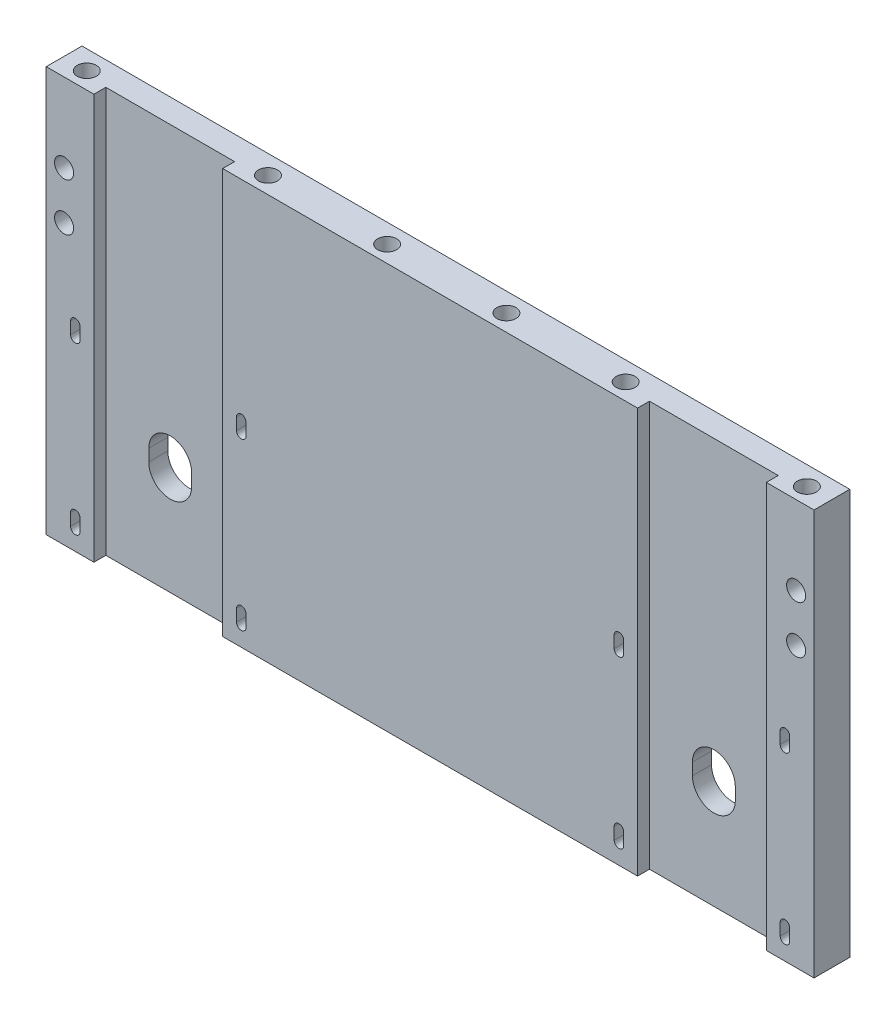
SolidWorks part; units mm, degrees
ref_plane "Płaszczyzna przednia" through (0, 0, 0) normal (0, 0, 1) x (1, 0, 0)
ref_plane "Płaszczyzna górna" through (0, 0, 0) normal (0, 1, 0) x (1, 0, 0)
ref_plane "Płaszczyzna prawa" through (0, 0, 0) normal (1, 0, 0) x (0, 0, -1)
sketch "Szkic1" plane through (0, 0, 0) normal (0, 0, 1) x (1, 0, 0)
  line L1 (161, -85) -> (-161, -85)
  line L2 (161, -85) -> (161, 85)
  line L3 (161, 85) -> (-161, 85)
  line L4 (-161, -85) -> (-161, 85)
  line L5 (161, -85) -> (-161, 85) construction
  line L6 (161, 85) -> (-161, -85) construction
  point P0 (0, 0)
  dimension "D1" = 322
  dimension "D2" = 170
extrude "Dodanie-wyciągnięcie1" add sketch "Szkic1" along normal blind 15
sketch "Szkic3" plane through (0, 0, 15) normal (0, 0, 1) x (1, 0, 0)
  line L0 (161, 85) -> (-161, 85) construction
  line L1 (-141, 85) -> (-87, 85)
  line L2 (-141, 85) -> (-141, -85)
  line L3 (-141, -85) -> (-87, -85)
  line L4 (-87, 85) -> (-87, -85)
  line L5 (-161, -85) -> (161, -85) construction
  line L6 (-161, 85) -> (-161, -85) construction
  line L7 (161, -85) -> (161, 85) construction
  line L8 (87, 85) -> (141, 85)
  line L9 (87, 85) -> (87, -85)
  line L10 (87, -85) -> (141, -85)
  line L11 (141, 85) -> (141, -85)
  dimension "D1" = 54
  dimension "D2" = 20
  dimension "D3" = 54
  dimension "D4" = 20
extrude "Wytnij-wyciągnięcie1" cut sketch "Szkic3" against normal blind 5
sketch "Szkic2" plane through (0, 0, 15) normal (0, 0, 1) x (1, 0, 0)
  line L0 (-161, -85) -> (-141, -85) construction
  line L1 (-161, 85) -> (-161, -85) construction
  line L3 (-150.8, -71.87) -> (-146.8, -71.87)
  line L4 (-150.8, -71.87) -> (-150.8, -76.87)
  line L5 (-150.8, -76.87) -> (-146.8, -76.87)
  line L6 (-146.8, -71.87) -> (-146.8, -76.87)
  circle A0 centre (-148.8, -76.87) radius 2
  circle A1 centre (-148.8, -71.87) radius 2
  dimension "D1" = 8.13
  dimension "D2" = 12.2
  dimension "D3" = 5
  dimension "D4" = 4
  dimension "D5" = 4
extrude "Wytnij-wyciągnięcie2" cut sketch "Szkic2" against normal blind 17.75 contours L3 A1 | L3 A1 | A1 L4 A0 L6 | L5 A0 | L5 A0 region at (-148.8, -71.0212, 15) region at (-148.8, -74.37, 15) region at (-148.8, -72.7188, 15) region at (-148.8, -76.0212, 15) region at (-148.8, -77.7188, 15)
pattern_linear "Szyk liniowy1" count 2 spacing 69.6 along (1, 0, 0) count 2 spacing 69.6 along (0, 1, 0) of "Wytnij-wyciągnięcie2"
sketch "Szkic5" plane through (0, 0, 0) normal (0, 0, -1) x (-1, 0, 0)
  line L0 (161, -85) -> (-161, -85) construction
  line L4 (161, 85) -> (161, -85) construction
  line L10 (150.5, -42.07) -> (77.5, -42.07)
  line L11 (150.5, -42.07) -> (150.5, -37.07)
  line L12 (150.5, -37.07) -> (77.5, -37.07)
  line L13 (77.5, -42.07) -> (77.5, -37.07)
  circle A0 centre (114, -42.07) radius 36.5
  circle A1 centre (114, -37.07) radius 36.5
  dimension "D1" = 42.93
  dimension "D3" = 73
  dimension "D4" = 5
  dimension "D5" = 73
  dimension "D2" = 47
extrude "Wytnij-wyciągnięcie3" cut sketch "Szkic5" against normal blind 2 contours L12 A1 A0 | L12 A0 | A0 A1 L10 L12 | L10 A1 | A1 L10 A0 | L12 A1 A0 | A1 A0 L10 | A1 L13 A0 | A0 A1 L12 | A1 L10 A0 | A1 A0 L11 | A1 region at (-114, -77.7538, 0) region at (-150.4743, -39.57, 0) region at (-150.3711, -41.2371, 0) region at (-114, -55.296, 0) region at (-114, -39.57, 0) region at (-150.3711, -37.9029, 0) region at (-150.328, -36.2538, 0) region at (-77.6289, -41.2371, 0) region at (-77.5257, -39.57, 0) region at (-114, -23.844, 0) region at (-77.6289, -37.9029, 0)
sketch "Szkic7" plane through (0, 0, 2) normal (0, 0, -1) x (-1, 0, 0)
  line L1 (105, -37.07) -> (123, -37.07)
  line L2 (105, -37.07) -> (105, -42.07)
  line L3 (105, -42.07) -> (123, -42.07)
  line L4 (123, -37.07) -> (123, -42.07)
  circle A0 centre (114, -42.07) radius 9
  arc A2 (77.5, -42.07) -> (150.5, -42.07) centre (114, -42.07) ccw construction
  circle A3 centre (114, -37.07) radius 9
  point P8 (114, -78.57)
  dimension "D1" = 18
  dimension "D2" = 18
extrude "Wytnij-wyciągnięcie4" cut sketch "Szkic7" against normal blind 17.75 contours A3 L3 A0 | L3 A3 | A0 A3 L3 L1 | A3 A0 L3 | L1 A3 A0 | L1 A3 A0 | A3 L2 A0 | L1 A0 | A0 A3 L1 | A3 A0 L4 | A3 L3 A0 region at (-114, -32.1697, 2) region at (-105.1059, -39.57, 2) region at (-105.5557, -37.8954, 2) region at (-114, -35.435, 2) region at (-114, -39.57, 2) region at (-105.5557, -41.2446, 2) region at (-114, -46.9703, 2) region at (-122.4443, -37.8954, 2) region at (-122.8941, -39.57, 2) region at (-114, -43.705, 2) region at (-122.4443, -41.2446, 2)
pattern_linear "Szyk liniowy2" count 2 spacing 228 along (1, 0, 0) of "Wytnij-wyciągnięcie2", "Szyk liniowy1", "Wytnij-wyciągnięcie3", "Wytnij-wyciągnięcie4"
sketch "Szkic8" plane through (0, 85, 0) normal (0, 1, 0) x (1, 0, 0)
  line L0 (-161, -15) -> (-161, 0) construction
  line L1 (-141, -15) -> (-161, -15) construction
  line L2 (161, -15) -> (161, 0) construction
  line L3 (161, -15) -> (141, -15) construction
  circle A0 centre (-151, -8) radius 4
  circle A1 centre (151, -8) radius 4
  dimension "D1" = 10
  dimension "D3" = 8
  dimension "D6" = 8
  dimension "D2" = 7
  dimension "D4" = 10
  dimension "D5" = 7
extrude "Wytnij-wyciągnięcie5" cut sketch "Szkic8" against normal blind 20
sketch "Szkic9" plane through (0, 85, 0) normal (0, 1, 0) x (1, 0, 0)
  line L0 (87, -15) -> (-87, -15) construction
  line L1 (-87, -10) -> (-87, -15) construction
  circle A0 centre (-75, -8) radius 4
  dimension "D1" = 8
  dimension "D2" = 7
  dimension "D3" = 12
extrude "Wytnij-wyciągnięcie6" cut sketch "Szkic9" against normal blind 20
pattern_linear "Szyk liniowy3" count 4 spacing 50 along (1, 0, 0) of "Wytnij-wyciągnięcie6"
sketch "Szkic10" plane through (0, 0, 15) normal (0, 0, 1) x (1, 0, 0)
  line L0 (-141, 85) -> (-161, 85) construction
  line L1 (-161, 85) -> (-161, -85) construction
  circle A0 centre (-153.5, 52) radius 4
  circle A1 centre (-153.5, 32) radius 4
  dimension "D1" = 53
  dimension "D3" = 8
  dimension "D4" = 8
  dimension "D2" = 20
  dimension "D5" = 7.5
extrude "Wytnij-wyciągnięcie7" cut sketch "Szkic10" against normal blind 20
sketch "Szkic11" plane through (0, 0, 15) normal (0, 0, 1) x (1, 0, 0)
  line L0 (161, 85) -> (141, 85) construction
  line L1 (161, -85) -> (161, 85) construction
  circle A0 centre (153.5, 32) radius 4
  circle A1 centre (153.5, 52) radius 4
  dimension "D1" = 53
  dimension "D2" = 8
  dimension "D3" = 8
  dimension "D4" = 7.5
  dimension "D5" = 20
extrude "Wytnij-wyciągnięcie8" cut sketch "Szkic11" against normal blind 20
